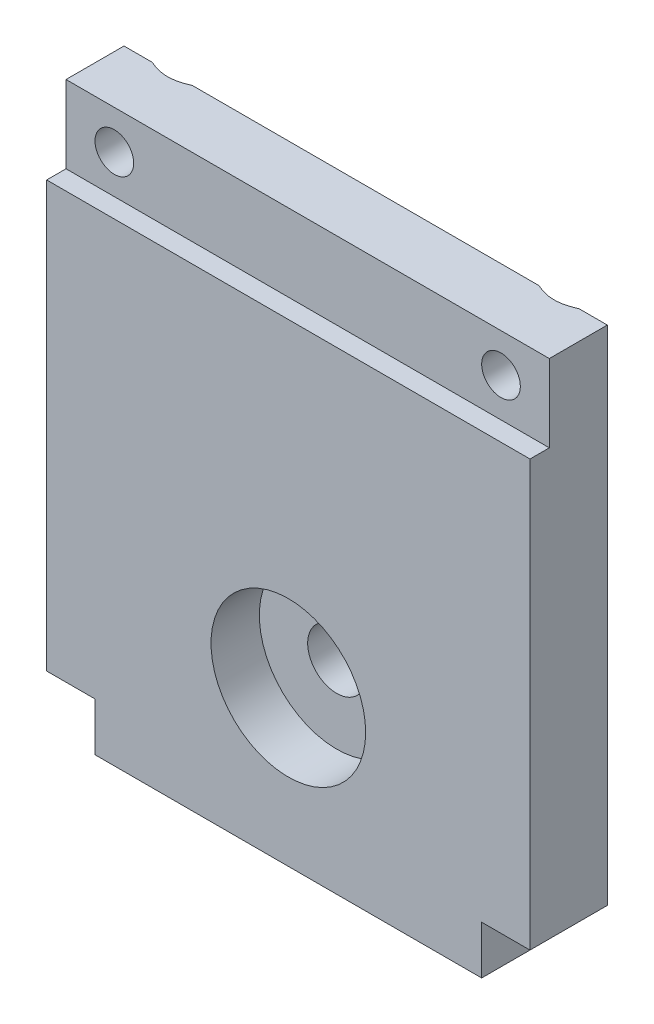
SolidWorks part; units mm, degrees
material "PVC rigide"
ref_plane "Plan de face" through (0, 0, 0) normal (0, 0, 1) x (1, 0, 0)
ref_plane "Plan de dessus" through (0, 0, 0) normal (0, 1, 0) x (1, 0, 0)
ref_plane "Plan de droite" through (0, 0, 0) normal (1, 0, 0) x (0, 0, -1)
sketch "Esquisse1" plane through (0, 0, 0) normal (0, 0, 1) x (1, 0, 0)
  line L0 (-25, -23.5) -> (-20, -23.5)
  line L1 (-25, 28.5) -> (25, 28.5)
  line L2 (-25, 28.5) -> (-25, -23.5)
  line L3 (-20, -28.5) -> (20, -28.5)
  line L4 (25, 28.5) -> (25, -23.5)
  line L5 (-20, -23.5) -> (-20, -28.5)
  line L6 (25, -23.5) -> (20, -23.5)
  line L7 (20, -23.5) -> (20, -28.5)
  line L8 (25, -28.5) -> (25, -23.5) construction
  line L9 (25, -28.5) -> (20, -28.5) construction
  line L10 (-25, -23.5) -> (-25, -28.5) construction
  line L11 (-25, -28.5) -> (-20, -28.5) construction
  line L12 (25, 28.5) -> (-25, -28.5) construction
  line L13 (-25, 28.5) -> (25, -28.5) construction
  point P9 (0, 0)
  dimension "D4" = 5
  dimension "D1" = 50
  dimension "D2" = 57
  dimension "D3" = 5
extrude "Boss.-Extru.1" add sketch "Esquisse1" along normal blind 8
sketch "Esquisse2" plane through (0, -28.5, 0) normal (0, -1, 0) x (1, 0, 0)
  line L0 (-25, 4) -> (25, 4) construction
  line L1 (-25, 8) -> (-25, 0) construction
  line L2 (25, 8) -> (25, 0) construction
  circle A0 centre (-15, 4) radius 2
  circle A1 centre (15, 4) radius 2
  dimension "D1" = 4
  dimension "D2" = 10
  dimension "D3" = 10
extrude "Enlèv. mat.-Extru.1" cut sketch "Esquisse2" against normal blind 10
sketch "Esquisse3" plane through (0, 0, 8) normal (0, 0, 1) x (1, 0, 0)
  line L0 (-25.973, 24.5) -> (39.229, 24.5) construction
  line L1 (25, 28.5) -> (-25, 28.5) construction
  line L2 (-25, 28.5) -> (-25, -23.5) construction
  line L3 (25, -23.5) -> (25, 28.5) construction
  circle A0 centre (-20, 24.5) radius 2
  circle A1 centre (20, 24.5) radius 2
  dimension "D2" = 4
  dimension "D1" = 4
  dimension "D3" = 5
  dimension "D4" = 5
extrude "Enlèv. mat.-Extru.2" cut sketch "Esquisse3" against normal through all
chamfer "Chanfrein1" distance 2.5 angle 45 2 edges at (22, 24.5, 0) (-18, 24.5, 0)
sketch "Esquisse4" plane through (0, 0, 8) normal (0, 0, 1) x (1, 0, 0)
  line L0 (-32.372, -12.5) -> (112.9613, -12.5) construction
  line L1 (0, -17.2825) -> (0, 28.5) construction
  line L3 (-20, -28.5) -> (20, -28.5) construction
  line L4 (25, 28.5) -> (-25, 28.5) construction
  circle A0 centre (0, -12.5) radius 8
  point P17 (0, -12.5)
  dimension "D1" = 16
  dimension "D2" = 16
extrude "Enlèv. mat.-Extru.3" cut sketch "Esquisse4" against normal blind 5
sketch "Esquisse5" plane through (0, 0, 3) normal (0, 0, 1) x (1, 0, 0)
  circle A0 centre (0, -12.5) radius 3
  circle A1 centre (0, -12.5) radius 8 construction
  dimension "D1" = 6
extrude "Enlèv. mat.-Extru.4" cut sketch "Esquisse5" against normal through all
sketch "Esquisse6" plane through (0, 0, 8) normal (0, 0, 1) x (1, 0, 0)
  line L0 (25, -23.5) -> (25, 28.5) construction
  line L1 (-25, 28.5) -> (25, 28.5)
  line L2 (-25, 28.5) -> (-25, 20.5)
  line L3 (-25, 20.5) -> (25, 20.5)
  line L4 (25, 28.5) -> (25, 20.5)
  circle A0 centre (-20, 24.5) radius 2 construction
  dimension "D1" = 4
extrude "Enlèv. mat.-Extru.5" cut sketch "Esquisse6" against normal blind 2
